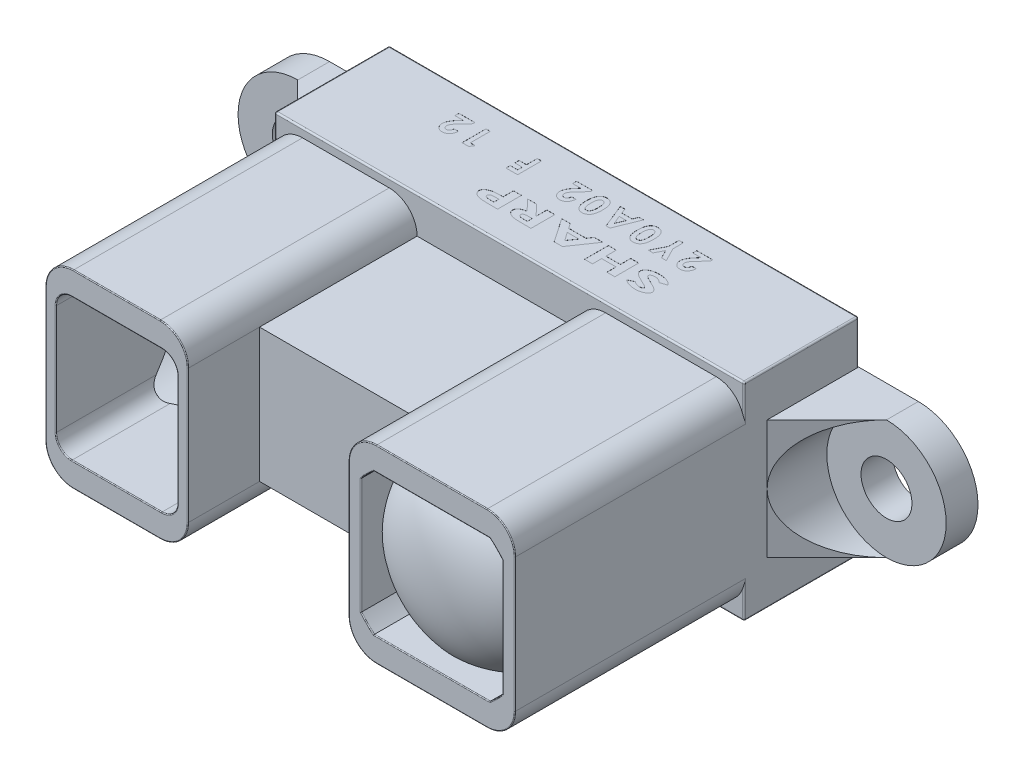
SolidWorks part; units mm, degrees
ref_plane "Front Plane" through (0, 0, 0) normal (0, 0, 1) x (1, 0, 0)
ref_plane "Top Plane" through (0, 0, 0) normal (0, 1, 0) x (1, 0, 0)
ref_plane "Right Plane" through (0, 0, 0) normal (1, 0, 0) x (0, 0, -1)
sketch "Sketch1" plane through (0, 0, 0) normal (0, 0, 1) x (1, 0, 0)
  line L0 (-18.5, 3.75) -> (-14.75, 3.75)
  line L1 (-14.75, -6.5) -> (14.75, -6.5)
  line L2 (-14.75, -6.5) -> (-14.75, -3.75)
  line L3 (-14.75, 6.5) -> (14.75, 6.5)
  line L4 (14.75, -6.5) -> (14.75, -3.75)
  line L5 (0, 0) -> (14.75, 6.5) construction
  line L6 (-14.75, 6.5) -> (0, 0) construction
  line L7 (-18.5, -3.75) -> (-14.75, -3.75)
  line L8 (18.5, -3.75) -> (14.75, -3.75)
  line L9 (18.5, 3.75) -> (14.75, 3.75)
  line L10 (-14.75, 3.75) -> (-14.75, 6.5)
  line L11 (14.75, 3.75) -> (14.75, 6.5)
  arc A0 (-18.5, 3.75) -> (-18.5, -3.75) centre (-18.5, 0) ccw
  arc A1 (18.5, -3.75) -> (18.5, 3.75) centre (18.5, 0) ccw
  circle A2 centre (-18.5, 0) radius 1.6
  circle A3 centre (18.5, 0) radius 1.6
  point P4 (0, 0)
  dimension "D2" = 37
  dimension "D3" = 18.5
  dimension "D4" = 7.5
  dimension "D5" = 7.5
  dimension "D7" = 3.2
  dimension "D8" = 3.2
  dimension "D1" = 29.5
  dimension "D6" = 13
extrude "Boss-Extrude1" add sketch "Sketch1" along normal blind 21.6
sketch "Sketch3" plane through (0, 0, 0) normal (0, 0, -1) x (-1, 0, 0)
  circle A0 centre (-18.5, 0) radius 3.75
  circle A1 centre (18.5, 0) radius 3.75
extrude "Cut-Extrude1" cut sketch "Sketch3" against normal through all from offset 2 offset against normal yes
sketch "Sketch4" plane through (0, -3.75, 0) normal (0, -1, 0) x (1, 0, 0)
  line L0 (22.25, 2) -> (18.5, 2)
  line L1 (18.5, 2) -> (14.75, 5.75)
  line L2 (14.75, 21.6) -> (14.75, 0) construction
  line L3 (14.75, 5.75) -> (14.75, 21.6)
  line L4 (14.75, 21.6) -> (22.25, 21.6)
  line L5 (22.25, 21.6) -> (22.25, 2)
  line L6 (-22.25, 2) -> (-18.5, 2)
  line L7 (-18.5, 2) -> (-14.75, 5.75)
  line L8 (-14.75, 21.6) -> (-14.75, 0) construction
  line L9 (-14.75, 5.75) -> (-14.75, 21.6)
  line L10 (-14.75, 21.6) -> (-22.25, 21.6)
  line L11 (-22.25, 21.6) -> (-22.25, 2)
  line L12 (14.75, 21.6) -> (14.75, 0) construction
  dimension "D1" = 45
  dimension "D2" = 45
extrude "Cut-Extrude2" cut sketch "Sketch4" against normal through all
sketch "Sketch5" plane through (0, 0, 21.6) normal (0, 0, 1) x (1, 0, 0)
  line L0 (14.75, -6.5) -> (14.75, 6.5) construction
  line L1 (-14.75, 6.5) -> (14.75, 6.5)
  line L2 (-14.75, 6.5) -> (-14.75, 4.2)
  line L3 (-14.75, 4.2) -> (14.75, 4.2)
  line L4 (14.75, 6.5) -> (14.75, 4.2)
  line L6 (-14.75, -6.5) -> (14.75, -6.5)
  line L7 (-14.75, -6.5) -> (-14.75, -4.2)
  line L8 (-14.75, -4.2) -> (14.75, -4.2)
  line L9 (14.75, -6.5) -> (14.75, -4.2)
  dimension "D1" = 8.4
  dimension "D2" = 4.2
extrude "Cut-Extrude3" cut sketch "Sketch5" along normal through all from offset 6.3 offset against normal yes
sketch "Sketch12" plane through (0, 0, 0) normal (0, 0, -1) x (-1, 0, 0)
  line L0 (14.75, -6.5) -> (-14.75, -6.5) construction
  line L1 (5.05, -6.5) -> (-5.05, -6.5)
  line L2 (5.05, -6.5) -> (5.05, -12.4)
  line L3 (5.05, -12.4) -> (-5.05, -12.4)
  line L4 (-5.05, -6.5) -> (-5.05, -12.4)
  point P6 (0, -6.5)
  dimension "D1" = 10.1
  dimension "D2" = 5.9
extrude "Boss-Extrude2" add sketch "Sketch12" against normal blind 1.2 from offset 3.3 offset against normal yes
sketch "Sketch13" plane through (0, -6.5, 0) normal (0, -1, 0) x (1, 0, 0)
  line L0 (-14.75, 15.3) -> (14.75, 15.3) construction
  line L1 (4.25, 4.5) -> (-5.05, 4.5)
  line L2 (4.25, 4.5) -> (4.25, 15.3)
  line L3 (4.25, 15.3) -> (-5.05, 15.3)
  line L4 (-5.05, 4.5) -> (-5.05, 15.3)
  dimension "D1" = 9.3
extrude "Cut-Extrude8" cut sketch "Sketch13" against normal up to surface (2.3 mm away) up to face at (0, -4.2, 18.45)
sketch "Sketch14" plane through (0, -4.2, 0) normal (0, -1, 0) x (1, 0, 0)
  line L0 (4.25, 4.5) -> (-5.05, 4.5) construction
  line L1 (-4.05, 4.5) -> (4.05, 4.5)
  line L2 (-4.05, 4.5) -> (-4.05, 9)
  line L3 (-4.05, 9) -> (4.05, 9)
  line L4 (4.05, 4.5) -> (4.05, 9)
  line L5 (-5.05, 15.3) -> (-5.05, 4.5) construction
  line L6 (-3.75, 4.8) -> (3.75, 4.8)
  line L7 (-3.75, 4.8) -> (-3.75, 8.7)
  line L8 (-3.75, 8.7) -> (3.75, 8.7)
  line L9 (3.75, 4.8) -> (3.75, 8.7)
  line L10 (-2.79, 7) -> (-2.29, 7)
  line L11 (-2.79, 7) -> (-2.79, 6.5)
  line L12 (-2.79, 6.5) -> (-2.29, 6.5)
  line L13 (-2.29, 7) -> (-2.29, 6.5)
  line L14 (-0.25, 7) -> (0.25, 7)
  line L15 (-0.25, 7) -> (-0.25, 6.5)
  line L16 (-0.25, 6.5) -> (0.25, 6.5)
  line L17 (0.25, 7) -> (0.25, 6.5)
  line L18 (2.29, 7) -> (2.79, 7)
  line L19 (2.29, 7) -> (2.29, 6.5)
  line L20 (2.29, 6.5) -> (2.79, 6.5)
  line L21 (2.79, 7) -> (2.79, 6.5)
  point P22 (0, 4.5)
  point P24 (0, 4.8)
  point P25 (0, 6.5)
  point P28 (-2.29, 6.75)
  point P29 (-0.25, 6.75)
  point P30 (2.29, 6.75)
  point P31 (-3.75, 6.75)
  line M23 (-5.05, 4.5) -> (4.25, 4.5)
  dimension "D1" = 4.5
  dimension "D2" = 1
  dimension "D3" = 0.3
  dimension "D4" = 0.3
  dimension "D5" = 0.3
  dimension "D6" = 0.5
  dimension "D7" = 0.5
  dimension "D8" = 0.5
  dimension "D9" = 0.5
  dimension "D10" = 0.5
  dimension "D11" = 0.5
  dimension "D12" = 2.54
  dimension "D13" = 2.54
extrude "Boss-Extrude3" add sketch "Sketch14" along normal through all contours L4 L3 L2 L9 L6 L7 L8 M23 | L17 L14 L15 L16 | L21 L20 L19 L18 | L12 L13 L10 L11 region at (-3.9573, -4.2, 6.75) region at (0, -4.2, 6.75)
sketch "Sketch15" plane through (0, -4.2, 0) normal (0, -1, 0) x (1, 0, 0)
  line L1 (-3.75, 4.8) -> (3.75, 4.8)
  line L2 (-3.75, 4.8) -> (-3.75, 8.7)
  line L3 (-3.75, 8.7) -> (3.75, 8.7)
  line L4 (3.75, 4.8) -> (3.75, 8.7)
extrude "Boss-Extrude4" add sketch "Sketch15" along normal blind 1 from offset 1.5
sketch "Sketch16" plane through (0, 0, 9) normal (0, 0, 1) x (1, 0, 0)
  line L0 (-4.05, -4.2) -> (-4.05, -4.8602)
  line L1 (-4.05, -12.4) -> (-4.05, -4.2) construction
  line L2 (-4.05, -4.8602) -> (-3.55, -4.8602)
  line L3 (-3.55, -4.8602) -> (-3.55, -5.7602)
  line L4 (-3.55, -5.7602) -> (3.55, -5.7602)
  line L5 (3.55, -5.7602) -> (3.55, -4.8)
  line L6 (3.55, -4.8) -> (4.05, -4.8)
  line L7 (4.05, -12.4) -> (4.05, -4.2) construction
  line L8 (4.05, -4.8) -> (4.05, -4.2)
  line L9 (-4.05, -12.4) -> (-4.05, -4.2) construction
  line L10 (-4.05, -4.2) -> (4.05, -4.2)
  dimension "D1" = 0.6
  dimension "D2" = 0.9
  dimension "D3" = 0.5
  dimension "D4" = 0.5
extrude "Cut-Extrude9" cut sketch "Sketch16" against normal up to surface (4.5 mm away) up to face at (4.45, -7.7, 4.5)
sketch "Sketch17" plane through (0, -12.4, 0) normal (0, -1, 0) x (-1, 0, 0)
  line L0 (4.05, -4.5) -> (4.05, -9) construction
  line L1 (-4.05, -4.5) -> (4.05, -4.5)
  line L2 (-4.05, -4.5) -> (-4.05, -4.6)
  line L3 (-4.05, -4.6) -> (4.05, -4.6)
  line L4 (4.05, -4.5) -> (4.05, -4.6)
  point P7 (4.05, -4.55)
  dimension "D1" = 0.05
extrude "Cut-Extrude10" cut sketch "Sketch17" against normal blind 0.1
chamfer "Chamfer3" distance 0.1 12 edges at (2.29, -12.4, 6.75) (2.54, -12.4, 7) (2.79, -12.4, 6.75) (2.54, -12.4, 6.5) (-0.25, -12.4, 6.75) (0, -12.4, 7) (0.25, -12.4, 6.75) (0, -12.4, 6.5) (-2.79, -12.4, 6.75) (-2.54, -12.4, 7) (-2.29, -12.4, 6.75) (-2.54, -12.4, 6.5)
sketch "Sketch18" plane through (0, 0, 9) normal (0, 0, 1) x (1, 0, 0)
  line L0 (-4.05, -12.4) -> (4.05, -12.4) construction
  line L1 (-0.75, -12.4) -> (0.75, -12.4)
  line L2 (-0.75, -12.4) -> (-0.75, -8.4)
  line L3 (-0.75, -8.4) -> (0.75, -8.4)
  line L4 (0.75, -12.4) -> (0.75, -8.4)
  line L5 (-4.05, -12.3) -> (-4.05, -4.8602) construction
  line L6 (-3.05, -8.4) -> (-2.05, -8.4)
  line L7 (-3.05, -8.4) -> (-3.05, -10.4)
  line L8 (-3.05, -10.4) -> (-2.05, -10.4)
  line L9 (-2.05, -8.4) -> (-2.05, -10.4)
  line L10 (2.05, -8.4) -> (3.05, -8.4)
  line L11 (2.05, -8.4) -> (2.05, -10.4)
  line L12 (2.05, -10.4) -> (3.05, -10.4)
  line L13 (3.05, -8.4) -> (3.05, -10.4)
  line L14 (4.05, -12.4) -> (4.05, -4.8) construction
  point P14 (0, -12.4)
  dimension "D1" = 2
  dimension "D2" = 1
  dimension "D3" = 1
  dimension "D4" = 2
  dimension "D5" = 2
  dimension "D6" = 1
  dimension "D7" = 2
  dimension "D8" = 1
  dimension "D9" = 1.5
  dimension "D10" = 4
extrude "Cut-Extrude11" cut sketch "Sketch18" against normal up to surface (0.3 mm away) up to face at (0, -9.55, 8.7)
sketch "Sketch19" plane through (0, 0, 15.3) normal (0, 0, 1) x (1, 0, 0)
  line L1 (-14.75, 6.5) -> (14.75, 6.5)
  line L2 (-14.75, 6.5) -> (-14.75, 4.2)
  line L3 (-14.75, 4.2) -> (14.75, 4.2)
  line L4 (14.75, 6.5) -> (14.75, 4.2)
  line L5 (-14.75, -4.2) -> (14.75, -4.2)
  line L6 (-14.75, -4.2) -> (-14.75, -6.5)
  line L7 (-14.75, -6.5) -> (14.75, -6.5)
  line L8 (14.75, -4.2) -> (14.75, -6.5)
extrude "Boss-Extrude5" add sketch "Sketch19" along normal up to surface (6.3 mm away) up to face at (0, 0, 21.6)
sketch "Sketch20" plane through (0, 0, 21.6) normal (0, 0, 1) x (1, 0, 0)
  line L1 (-14.75, 6.5) -> (14.75, 6.5)
  line L2 (-14.75, 6.5) -> (-14.75, -6.5)
  line L3 (-14.75, -6.5) -> (14.75, -6.5)
  line L4 (14.75, 6.5) -> (14.75, -6.5)
  line L5 (-7.55, -5.95) -> (-13, -5.95)
  line L6 (-5.8, -4.2) -> (-5.8, 4.2)
  line L7 (-7.55, 5.95) -> (-13, 5.95)
  line L8 (-14.75, -4.2) -> (-14.75, 4.2)
  line L9 (-5.8, -5.95) -> (-14.75, 5.95) construction
  line L10 (-5.8, 5.95) -> (-14.75, -5.95) construction
  line L11 (13, -5.95) -> (6.05, -5.95)
  line L12 (14.75, -4.2) -> (14.75, 4.2)
  line L13 (13, 5.95) -> (6.05, 5.95)
  line L14 (4.3, -4.2) -> (4.3, 4.2)
  line L15 (14.75, -5.95) -> (4.3, 5.95) construction
  line L16 (14.75, 5.95) -> (4.3, -5.95) construction
  arc A0 (-13, 5.95) -> (-14.75, 4.2) centre (-13, 4.2) ccw
  arc A1 (-13, -5.95) -> (-14.75, -4.2) centre (-13, -4.2) cw
  arc A2 (-7.55, -5.95) -> (-5.8, -4.2) centre (-7.55, -4.2) ccw
  arc A3 (-5.8, 4.2) -> (-7.55, 5.95) centre (-7.55, 4.2) ccw
  arc A4 (14.75, 4.2) -> (13, 5.95) centre (13, 4.2) ccw
  arc A5 (13, -5.95) -> (14.75, -4.2) centre (13, -4.2) ccw
  arc A6 (6.05, -5.95) -> (4.3, -4.2) centre (6.05, -4.2) cw
  arc A7 (6.05, 5.95) -> (4.3, 4.2) centre (6.05, 4.2) ccw
  point P6 (-10.275, 0)
  point P11 (9.525, 0)
  line M17 (14.75, -6.5) -> (14.75, 6.5)
  line M18 (14.75, 6.5) -> (-14.75, 6.5)
  line M19 (-14.75, 6.5) -> (-14.75, -6.5)
  line M20 (-14.75, -6.5) -> (14.75, -6.5)
  dimension "D7" = 1.75
  dimension "D1" = 11.9
  dimension "D2" = 8.95
  dimension "D3" = 4.475
  dimension "D4" = 19.8
  dimension "D5" = 11.9
  dimension "D6" = 10.45
extrude "Cut-Extrude12" cut sketch "Sketch20" against normal blind 4.5 contours A7 L13 A4 A0 L7 A3 L6 A2 L5 A1 A5 L11 A6 L14 M17 M18 M19 M20 region at (-0.5834, 0, 21.6)
sketch "Sketch21" plane through (0, 0, 21.6) normal (0, 0, 1) x (1, 0, 0)
  line L0 (-14.75, 6.5) -> (14.75, 6.5)
  line L1 (-14.75, 6.5) -> (-14.75, -6.5)
  line L2 (-14.75, -6.5) -> (14.75, -6.5)
  line L3 (14.75, 6.5) -> (14.75, -6.5)
  line L4 (-7.55, -5.95) -> (-13, -5.95)
  line L5 (-5.8, -4.2) -> (-5.8, 4.2)
  line L6 (-7.55, 5.95) -> (-13, 5.95)
  line L7 (-14.75, -4.2) -> (-14.75, 4.2)
  line L8 (-5.8, -5.95) -> (-14.75, 5.95) construction
  line L9 (-5.8, 5.95) -> (-14.75, -5.95) construction
  line L10 (13, -5.95) -> (6.05, -5.95)
  line L11 (14.75, -4.2) -> (14.75, 4.2)
  line L12 (13, 5.95) -> (6.05, 5.95)
  line L13 (4.3, -4.2) -> (4.3, 4.2)
  line L14 (14.75, -5.95) -> (4.3, 5.95) construction
  line L15 (14.75, 5.95) -> (4.3, -5.95) construction
  line L16 (-5.8, 4.2) -> (4.3, 4.2)
  line L17 (4.3, -4.2) -> (-5.8, -4.2)
  arc A0 (-13, 5.95) -> (-14.75, 4.2) centre (-13, 4.2) ccw
  arc A1 (-13, -5.95) -> (-14.75, -4.2) centre (-13, -4.2) cw
  arc A2 (-7.55, -5.95) -> (-5.8, -4.2) centre (-7.55, -4.2) ccw
  arc A3 (-5.8, 4.2) -> (-7.55, 5.95) centre (-7.55, 4.2) ccw
  arc A4 (14.75, 4.2) -> (13, 5.95) centre (13, 4.2) ccw
  arc A5 (13, -5.95) -> (14.75, -4.2) centre (13, -4.2) ccw
  arc A6 (6.05, -5.95) -> (4.3, -4.2) centre (6.05, -4.2) cw
  arc A7 (6.05, 5.95) -> (4.3, 4.2) centre (6.05, 4.2) ccw
  point P4 (-10.275, 0)
  point P9 (9.525, 0)
  line M23 (6.05, -5.95) -> (13, -5.95)
  arc M24 (13, -5.95) -> (14.75, -4.2) centre (13, -4.2) ccw
  arc M26 (14.75, 4.2) -> (13, 5.95) centre (13, 4.2) ccw
  line M27 (13, 5.95) -> (6.05, 5.95)
  arc M28 (6.05, 5.95) -> (4.3, 4.2) centre (6.05, 4.2) ccw
  arc M30 (4.3, -4.2) -> (6.05, -5.95) centre (6.05, -4.2) ccw
  dimension "D7" = 1.75
  dimension "D1" = 11.9
  dimension "D2" = 8.95
  dimension "D3" = 4.475
  dimension "D4" = 19.8
  dimension "D5" = 11.9
  dimension "D6" = 10.45
  dimension "D8" = 8.4
  dimension "D9" = 4.2
extrude "Cut-Extrude13" cut sketch "Sketch21" against normal up to surface (12.6 mm away) contours A2 L4 A1 L1 L2 L3 L17 M24 M23 M30 | A3 L16 L3 L0 L1 A0 L6 M28 M27 M26 region at (-0.3899, 5.6206, 21.6) region at (-0.3899, -5.6206, 21.6) up to face at (2.55, -9.4, 9)
sketch "Sketch23" plane through (0, 0, 21.6) normal (0, 0, 1) x (1, 0, 0)
  line L0 (-14.75, 6.5) -> (14.75, 6.5)
  line L1 (-14.75, 6.5) -> (-14.75, -6.5)
  line L2 (-14.75, -6.5) -> (14.75, -6.5)
  line L3 (14.75, 6.5) -> (14.75, -6.5)
  line L4 (-7.55, -5.95) -> (-13, -5.95)
  line L5 (-5.8, -4.2) -> (-5.8, 4.2)
  line L6 (-7.55, 5.95) -> (-13, 5.95)
  line L7 (-14.75, -4.2) -> (-14.75, 4.2)
  line L8 (-5.8, -5.95) -> (-14.75, 5.95) construction
  line L9 (-5.8, 5.95) -> (-14.75, -5.95) construction
  line L10 (13, -5.95) -> (6.05, -5.95)
  line L11 (14.75, -4.2) -> (14.75, 4.2)
  line L12 (13, 5.95) -> (6.05, 5.95)
  line L13 (4.3, -4.2) -> (4.3, 4.2)
  line L14 (14.75, -5.95) -> (4.3, 5.95) construction
  line L15 (14.75, 5.95) -> (4.3, -5.95) construction
  line L16 (-5.8, 4.2) -> (4.3, 4.2)
  line L17 (4.3, -4.2) -> (-5.8, -4.2)
  line L18 (-5.05, -6.5) -> (-5.05, -4.2)
  line L19 (4.25, -6.5) -> (4.25, -4.2)
  arc A0 (-13, 5.95) -> (-14.75, 4.2) centre (-13, 4.2) ccw
  arc A1 (-13, -5.95) -> (-14.75, -4.2) centre (-13, -4.2) cw
  arc A2 (-7.55, -5.95) -> (-5.8, -4.2) centre (-7.55, -4.2) ccw
  arc A3 (-5.8, 4.2) -> (-7.55, 5.95) centre (-7.55, 4.2) ccw
  arc A4 (14.75, 4.2) -> (13, 5.95) centre (13, 4.2) ccw
  arc A5 (13, -5.95) -> (14.75, -4.2) centre (13, -4.2) ccw
  arc A6 (6.05, -5.95) -> (4.3, -4.2) centre (6.05, -4.2) cw
  arc A7 (6.05, 5.95) -> (4.3, 4.2) centre (6.05, 4.2) ccw
  point P4 (-10.275, 0)
  point P9 (9.525, 0)
  line M21 (6.05, -5.95) -> (13, -5.95)
  arc M22 (13, -5.95) -> (14.75, -4.2) centre (13, -4.2) ccw
  arc M24 (14.75, 4.2) -> (13, 5.95) centre (13, 4.2) ccw
  line M25 (13, 5.95) -> (6.05, 5.95)
  arc M26 (6.05, 5.95) -> (4.3, 4.2) centre (6.05, 4.2) ccw
  arc M28 (4.3, -4.2) -> (6.05, -5.95) centre (6.05, -4.2) ccw
  dimension "D7" = 1.75
  dimension "D1" = 11.9
  dimension "D2" = 8.95
  dimension "D3" = 4.475
  dimension "D4" = 19.8
  dimension "D5" = 11.9
  dimension "D6" = 10.45
  dimension "D8" = 8.4
extrude "Cut-Extrude14" cut sketch "Sketch23" against normal blind 14.4 contours A3 L16 L3 L0 L1 A0 L6 M26 M25 M24 | A2 L4 A1 L1 L2 L18 L17 | L2 L3 M22 M21 M28 region at (-0.3899, 5.6206, 21.6) region at (-14.3079, -5.5079, 21.6) region at (9.4409, -6.089, 21.6)
sketch "Sketch24" plane through (0, 0, 21.6) normal (0, 0, 1) x (1, 0, 0)
  line L0 (13, 5.95) -> (6.05, 5.95) construction
  line L1 (-12.676, -3.6126) -> (-7.874, -3.6126)
  line L2 (-12.676, -3.6126) -> (-12.676, 3.6126)
  line L3 (-12.676, 3.6126) -> (-7.874, 3.6126)
  line L4 (-7.874, -3.6126) -> (-7.874, 3.6126)
  line L5 (-12.676, -3.6126) -> (-7.874, 3.6126) construction
  line L6 (-12.676, 3.6126) -> (-7.874, -3.6126) construction
  line L7 (5.8836, -4.45) -> (13.1664, -4.45)
  line L8 (5.075, -3.6414) -> (5.075, 3.6414)
  line L9 (5.8836, 4.45) -> (13.1664, 4.45)
  line L10 (13.975, -3.6414) -> (13.975, 3.6414)
  line L11 (5.4591, -4.0659) -> (13.5909, 4.0659) construction
  line L12 (5.4591, 4.0659) -> (13.5909, -4.0659) construction
  line L13 (-7.55, 5.95) -> (-13, 5.95) construction
  line L14 (6.05, -5.95) -> (13, -5.95) construction
  arc A0 (5.8836, 4.45) -> (5.075, 3.6414) centre (9.525, 0) ccw
  arc A1 (13.975, 3.6414) -> (13.1664, 4.45) centre (9.525, 0) ccw
  arc A2 (13.1664, -4.45) -> (13.975, -3.6414) centre (9.525, 0) ccw
  arc A3 (5.075, -3.6414) -> (5.8836, -4.45) centre (9.525, 0) ccw
  point P0 (-10.275, 0)
  point P5 (9.525, 0)
  point P15 (9.525, 5.95)
  point P19 (-10.275, 5.95)
  dimension "D3" = 11.5
  dimension "D1" = 1.5
  dimension "D2" = 1.5
extrude "Cut-Extrude15" cut sketch "Sketch24" against normal blind 4 contours L8 A3 L7 A2 L10 A1 L9 A0 region at (9.525, 0, 21.6)
sketch "Sketch25" plane through (0, 0, 0) normal (0, 1, 0) x (1, 0, 0)
  line L0 (9.525, -17.6) -> (9.525, -29.2073) construction
  line L1 (5.8836, -17.6) -> (13.1664, -17.6) construction
  line L2 (9.525, -17.6) -> (15.275, -17.6)
  line L3 (13, -21.6) -> (6.05, -21.6) construction
  line L4 (15.275, -20.6) -> (15.275, -14.6) construction
  line L5 (8.525, -21.6) -> (10.525, -21.6) construction
  line L6 (9.525, -17.6) -> (9.525, -21.6)
  spline S0 degree 3 poles (15.275, -17.6) (15.275, -18.6) (14.525, -21.6) (9.525, -21.6) knots 0 0 0 0 1 1 1 1
  dimension "D2" = 3
  dimension "D4" = 15
  dimension "D1" = 5.75
  dimension "D3" = 90
  dimension "D5" = 90
revolve "Revolve1" add sketch "Sketch25" angle 360 about L0
sketch "Sketch26" plane through (0, 0, 21.6) normal (0, 0, 1) x (1, 0, 0)
  line L0 (-7.55, 5.95) -> (-13, 5.95) construction
  line L1 (-13.1, -4.45) -> (-7.45, -4.45)
  line L2 (-14.1, -3.45) -> (-14.1, 3.45)
  line L3 (-13.1, 4.45) -> (-7.45, 4.45)
  line L4 (-6.45, -3.45) -> (-6.45, 3.45)
  line L5 (-14.1, -4.45) -> (-6.45, 4.45) construction
  line L6 (-14.1, 4.45) -> (-6.45, -4.45) construction
  line L9 (-7.55, 5.95) -> (-13, 5.95) construction
  line L10 (-14.75, 4.2) -> (-14.75, -4.2) construction
  arc A0 (-13.1, -4.45) -> (-14.1, -3.45) centre (-13.1, -3.45) cw
  arc A1 (-7.45, -4.45) -> (-6.45, -3.45) centre (-7.45, -3.45) ccw
  arc A2 (-7.45, 4.45) -> (-6.45, 3.45) centre (-7.45, 3.45) cw
  arc A3 (-14.1, 3.45) -> (-13.1, 4.45) centre (-13.1, 3.45) cw
  point P0 (-10.275, 0)
  point P8 (-10.275, 5.95)
  dimension "D3" = 1
  dimension "D1" = 1.5
  dimension "D2" = 0.65
extrude "Cut-Extrude16" cut sketch "Sketch26" against normal blind 6
sketch "Sketch27" plane through (0, 0, 15.6) normal (0, 0, 1) x (1, 0, 0)
  line L0 (-7.55, 5.95) -> (-13, 5.95) construction
  line L1 (-6.45, -2.2742) -> (-6.45, 2.2742)
  line L2 (-14.1, -2.2742) -> (-14.1, 2.2742)
  arc A0 (-14.1, -2.2742) -> (-6.45, -2.2742) centre (-10.275, 0) ccw
  arc A1 (-6.45, 2.2742) -> (-14.1, 2.2742) centre (-10.275, 0) ccw
  point P5 (-10.275, 5.95)
extrude "Cut-Extrude17" cut sketch "Sketch27" against normal blind 4
sketch "Sketch28" plane through (0, 0, 0) normal (0, 1, 0) x (1, 0, 0)
  line L0 (-10.275, -11.6) -> (-10.275, -28.487) construction
  line L1 (-14.1, -11.6) -> (-6.45, -11.6) construction
  line L2 (-10.275, -11.6) -> (-5.825, -11.6)
  line L4 (-5.825, -17.6) -> (-5.825, -5.6) construction
  line L5 (-16.275, -15.6) -> (-4.275, -15.6) construction
  line L6 (-10.275, -11.6) -> (-10.275, -15.6)
  spline S0 degree 3 poles (-5.825, -11.6) (-5.825, -12.6) (-6.275, -15.6) (-10.275, -15.6) knots 0 0 0 0 1 1 1 1
  dimension "D3" = 3
  dimension "D5" = 12
  dimension "D1" = 4.45
  dimension "D2" = 4
  dimension "D4" = 90
  dimension "D6" = 90
revolve "Revolve2" add sketch "Sketch28" angle 360 about L0
sketch "Sketch30" plane through (14.75, 0, 0) normal (1, 0, 0) x (0, 0, -1)
  line L1 (-26.5725, 10.2761) -> (-14.1065, 10.2761)
  line L2 (-26.5725, 10.2761) -> (-26.5725, -3.5581)
  line L3 (-26.5725, -3.5581) -> (-14.1065, -3.5581)
  line L4 (-14.1065, 10.2761) -> (-14.1065, -3.5581)
  line L5 (-26.5725, 10.2761) -> (-14.1065, -3.5581) construction
  line L6 (-26.5725, -3.5581) -> (-14.1065, 10.2761) construction
  point P0 (-20.3395, 3.359)
extrude "Cut-Extrude18" cut sketch "Sketch30" along normal through all
sketch "Sketch31" plane through (4.3, 0, 0) normal (-1, 0, 0) x (0, 0, 1)
  line L1 (17.2681, 3.5521) -> (20.2652, 3.5521)
  line L2 (17.2681, 3.5521) -> (17.2681, -3.3932)
  line L3 (17.2681, -3.3932) -> (20.2652, -3.3932)
  line L4 (20.2652, 3.5521) -> (20.2652, -3.3932)
extrude "Cut-Extrude19" cut sketch "Sketch31" along normal blind 4
sketch "Sketch32" plane through (0, 0, 7.2) normal (0, 0, 1) x (1, 0, 0)
  line L0 (4.25, -4.2) -> (4.25, -6.5)
  line L1 (4.25, -6.5) -> (5.05, -6.5)
  line L2 (5.05, -6.5) -> (5.05, -5.6361)
  line L3 (4.25, -4.2) -> (4.3, -4.2)
  line L4 (0, 5.6203) -> (0, -5.6361) construction
  arc A0 (4.3, -4.2) -> (6.05, -5.95) centre (6.05, -4.2) ccw construction
  arc A1 (4.3, -4.2) -> (5.05, -5.6361) centre (6.05, -4.2) ccw
extrude "Cut-Extrude20" cut sketch "Sketch32" against normal up to surface (2.7 mm away) up to face at (0, -6.9301, 4.5)
sketch "Sketch33" plane through (0, 6.5, 0) normal (0, 1, 0) x (1, 0, 0)
  line L0 (-8.9857, -1.5) -> (7.75, -1.5) construction
  line L1 (-4.3049, -4) -> (7.75, -4) construction
  line L2 (14.75, 0) -> (-14.75, 0) construction
  text T0 "<b>SHARP</b>" font "Century Gothic" height 1.5
  text T1 "<b>2Y0A02  F  12</b>" font "Century Gothic" height 1.5
  point P4 (-0.6178, -1.5)
  dimension "D1" = 2.5
  dimension "D2" = 7
  dimension "D3" = 1.5
extrude "Cut-Extrude21" cut sketch "Sketch33" against normal blind 0.005
sketch "Sketch34" plane through (0, 0, 0) normal (0, 0, -1) x (-1, 0, 0)
  line L0 (-14.75, 6.5) -> (14.75, 6.5) construction
  line L1 (-13.75, -5.5) -> (-5.05, -5.5)
  line L2 (-13.75, -5.5) -> (-13.75, 5.5)
  line L3 (-13.75, 5.5) -> (13.75, 5.5)
  line L4 (13.75, -5.5) -> (13.75, 5.5)
  line L5 (-13.75, -5.5) -> (13.75, 5.5) construction
  line L6 (-13.75, 5.5) -> (13.75, -5.5) construction
  line L7 (-14.75, -6.5) -> (-14.75, -3.75) construction
  line L8 (-5.05, -6.5) -> (-5.05, -5.5)
  line L9 (-5.05, -6.5) -> (5.05, -6.5)
  line L10 (5.05, -6.5) -> (5.05, -5.5)
  line L11 (5.05, -5.5) -> (13.75, -5.5)
  point P0 (0, 0)
  dimension "D1" = 1
  dimension "D2" = 1
extrude "Cut-Extrude22" cut sketch "Sketch34" against normal up to surface (3.3 mm away) up to face at (0, -9.45, 3.3)
fillet "Fillet1" radius 0.1 29 edges at (-14.75, 5.125, 0) (-14.75, 5.35, 7.2) (-14.75, 6.5, 3.6) (0, 6.5, 7.2) (14.75, 5.35, 7.2) (14.75, 6.5, 3.6) (14.75, -5.125, 0) (14.75, 5.125, 0) (0, 6.5, 0) (5.05, -5.5, 1.65) (5.05, -6, 0) (-5.05, -5.5, 1.65) (-5.05, -6, 0) (-9.4, -5.5, 0) (-13.75, 0, 0) (0, 5.5, 0) (13.75, 0, 0) (9.4, -5.5, 0) (9.9, -6.5, 0) (14.75, -5.35, 7.2) (14.75, -6.5, 3.6) (5.05, -6.5, 5.85) (5.05, -6.5, 1.65) (9.9, -6.5, 7.2) (-9.9, -6.5, 0) (-5.05, -6.5, 1.65) (-14.75, -6.5, 3.6) (-9.9, -6.5, 7.2) (-14.75, -5.35, 7.2)
chamfer "Chamfer4" distance 1 2 edges at (-12.4753, -3.868, 15.6) (-8.0747, -3.868, 15.6)
chamfer "Chamfer5" distance 1 2 edges at (-12.4753, 3.868, 15.6) (-8.0747, 3.868, 15.6)
fillet "Fillet2" radius 0.05 30 edges at (-14.75, 0, 21.6) (-14.2374, 5.4374, 21.6) (-10.275, 5.95, 21.6) (-6.3126, 5.4374, 21.6) (-5.8, 0, 21.6) (-6.3126, -5.4374, 21.6) (-10.275, -5.95, 21.6) (-14.2374, -5.4374, 21.6) (-10.275, -4.45, 21.6) (-6.7429, -4.1571, 21.6) (-6.45, 0, 21.6) (-6.7429, 4.1571, 21.6) (-10.275, 4.45, 21.6) (-13.8071, 4.1571, 21.6) (-14.1, 0, 21.6) (-13.8071, -4.1571, 21.6) (9.525, -4.45, 21.6) (13.5909, -4.0659, 21.6) (13.975, 0, 21.6) (13.5909, 4.0659, 21.6) (9.525, 4.45, 21.6) (5.4591, 4.0659, 21.6) (5.075, 0, 21.6) (5.4591, -4.0659, 21.6) (4.8126, -5.4374, 21.6) (4.3, 0, 21.6) (4.8126, 5.4374, 21.6) (14.2374, 5.4374, 21.6) (14.75, 0, 21.6) (14.2374, -5.4374, 21.6)
